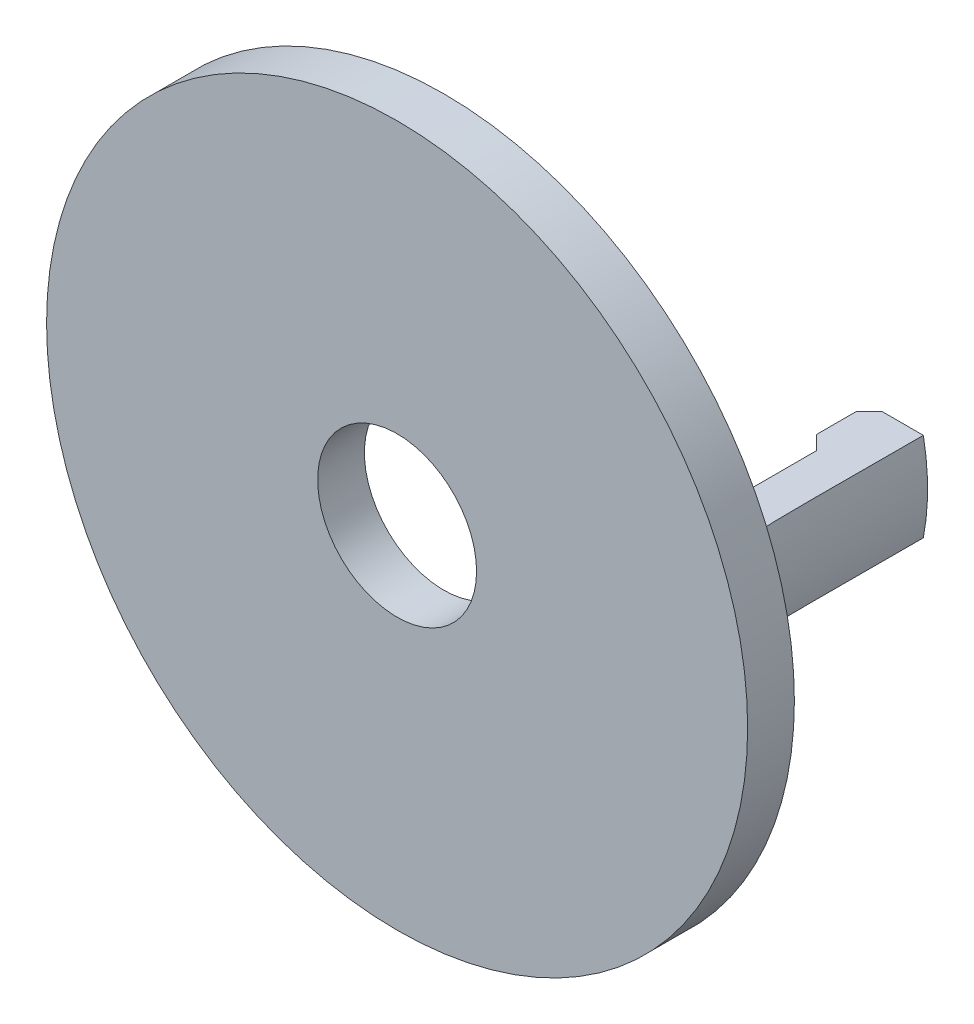
SolidWorks part; units mm, degrees
ref_plane "Front" through (0, 0, 0) normal (0, 0, 1) x (1, 0, 0)
ref_plane "Top" through (0, 0, 0) normal (0, 1, 0) x (1, 0, 0)
ref_plane "Right" through (0, 0, 0) normal (1, 0, 0) x (0, 0, -1)
sketch "Sketch1" plane through (0, 0, 0) normal (0, 0, 1) x (1, 0, 0)
  circle A0 centre (0, 0) radius 26.5
  circle A1 centre (0, 0) radius 37.5
  circle A2 centre (-2, 0) radius 26.5
  dimension "D1" = 53
  dimension "D2" = 75
  dimension "D3" = 2
sketch "Sketch4" plane through (0, 0, 0) normal (0, 0, 1) x (1, 0, 0)
  circle A0 centre (0, 0) radius 37.5
  dimension "D1" = 75
extrude "Boss-Extrude2" add sketch "Sketch4" along normal blind 5
sketch "Sketch5" plane through (0, 0, 5) normal (0, 0, 1) x (1, 0, 0)
  circle A0 centre (0, 0) radius 8.5
  dimension "D1" = 17
extrude "Cut-Extrude1" cut sketch "Sketch5" against normal through all
sketch "Sketch6" plane through (0, 0, 0) normal (0, 1, 0) x (1, 0, 0)
  line L0 (20, 0) -> (26.5, 0) construction
  line L1 (26.5, 0) -> (26.5, 27) construction
  line L2 (17.3536, 0) -> (26.5, 0)
  line L3 (26.5, 27) -> (20, 27) construction
  line L4 (20, 27) -> (18.5, 25.5) construction
  line L5 (18.5, 21) -> (20, 19.5) construction
  line L6 (20, 19.5) -> (20, 0) construction
  line L7 (20.25, 19.6036) -> (20.25, 2.8964)
  line L8 (20, 3) -> (17, 0) construction
  line L9 (20.25, 19.6036) -> (18.75, 21.1036)
  line L10 (18.5, 25.5) -> (18.5, 21) construction
  line L11 (18.75, 21.1036) -> (18.75, 25.3964)
  line L12 (26.5, 0) -> (26.5, 26.75)
  line L13 (17, 0) -> (20, 0) construction
  line L14 (20.25, 2.8964) -> (17.3536, 0)
  line L15 (18.75, 25.3964) -> (20.1036, 26.75)
  line L16 (20.1036, 26.75) -> (26.5, 26.75)
  line L17 (25, 26.5113) -> (25, 41.0721) construction
  line L18 (25, 12.4795) -> (25, 18.7128) construction
  spline S0 degree 3 poles (25, 26.75) (25, 22.7282) (24.9901, 20.5425) (25.0119, 14.9424) (24.7749, 4.9839) (26.5, 0) knots 0 0 0 0 0.446605 0.546605 1 1 1 1
  dimension "D1" = 135
  dimension "D2" = 6.5
  dimension "D3" = 8
  dimension "D4" = 27
  dimension "D5" = 7.5
  dimension "D6" = 0.25
  dimension "D7" = 0.25
  dimension "D8" = 0.25
  dimension "D9" = 0.25
  dimension "D10" = 3
  dimension "D11" = 3
  dimension "D12" = 0.25
  dimension "D13" = 1.5
  dimension "D14" = 0.25
extrude "Boss-Extrude3" add sketch "Sketch6" along normal blind 4.75 and the other way blind 4.75 contours L16 L15 L11 L9 L7 L14 L2 | L12 L16 region at (22.4479, 0, -13.2155) region at (25.7982, 0, -14.9997)
extrude "Cut-Extrude2" cut sketch "Sketch1" against normal through all contours A1 A2 A0 region at (-36.4393, 0, 0)
ref_axis "Axis1" through (0, 0, 0) along (0, 0, -1)
revolve "Cut-Revolve1" cut sketch "Sketch6<4>" angle 360 about axis through (0, 0, 0) along (0, 0, -1) region at (25.7982, 0, -14.9997)
sketch "Sketch6<4>" plane through (0, 0, 0) normal (0, 1, 0) x (1, 0, 0) same geometry as "Sketch6"
mirror "Mirror1" about plane through (0, 0, 0) normal (1, 0, 0) of "Boss-Extrude3", "Cut-Extrude2", "Cut-Revolve1"
equation "\"female_make_room\"= 0.25"
equation "\"D6@Sketch6\"=\"female_make_room\""
equation "\"D8@Sketch6\"=\"female_make_room\""
equation "\"D7@Sketch6\"=\"female_make_room\""
equation "\"D9@Sketch6\"=\"female_make_room\""
equation "\"D12@Sketch6\"=\"female_make_room\""
equation "\"D14@Sketch6\"=\"female_make_room\""
